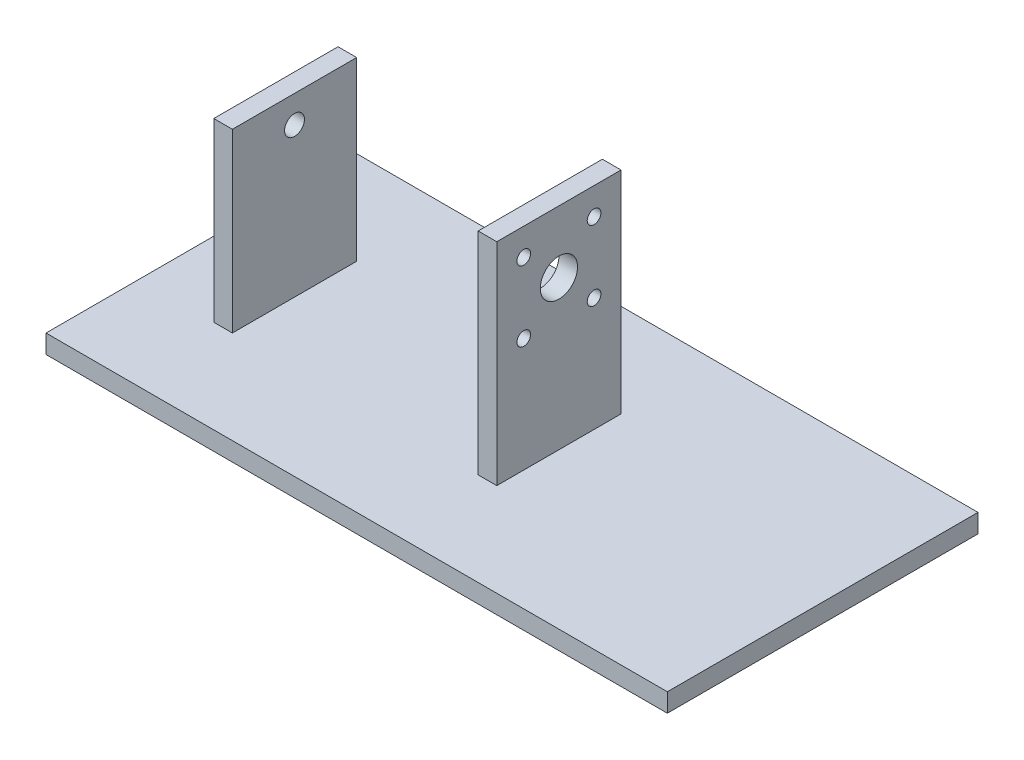
SolidWorks part; units mm, degrees
ref_plane "Front Plane" through (0, 0, 0) normal (0, 0, 1) x (1, 0, 0)
ref_plane "Top Plane" through (0, 0, 0) normal (0, 1, 0) x (1, 0, 0)
ref_plane "Right Plane" through (0, 0, 0) normal (1, 0, 0) x (0, 0, -1)
sketch "Sketch1" plane through (0, 0, 0) normal (0, 1, 0) x (1, 0, 0)
  line L1 (50, 25) -> (-50, 25)
  line L2 (50, 25) -> (50, -25)
  line L3 (50, -25) -> (-50, -25)
  line L4 (-50, 25) -> (-50, -25)
  line L5 (50, 25) -> (-50, -25) construction
  line L6 (50, -25) -> (-50, 25) construction
  line L7 (-38, 10) -> (-35, 10)
  line L8 (-38, 10) -> (-38, -10)
  line L9 (-38, -10) -> (-35, -10)
  line L10 (-35, 10) -> (-35, -10)
  line L11 (4.55, 10) -> (7.55, 10)
  line L12 (4.55, 10) -> (4.55, -10)
  line L13 (4.55, -10) -> (7.55, -10)
  line L14 (7.55, 10) -> (7.55, -10)
  point P0 (0, 0)
  point P14 (-35, 0)
  point P15 (7.55, 0)
  dimension "D1" = 100
  dimension "D2" = 50
  dimension "D3" = 39.55
  dimension "D4" = 3
  dimension "D5" = 20
  dimension "D6" = 12
extrude "Boss-Extrude1" add sketch "Sketch1" along normal blind 3 contours L7 L10 L9 L4 L3 L2 L1 L11 L14 L13 L12 region at (0.3744, 0, 0)
extrude "Boss-Extrude2" add sketch "Sketch1<3>" along normal blind 37 contours L14 L11 L12 L13 region at (6.05, 0, 0)
sketch "Sketch1<3>" plane through (0, 0, 0) normal (0, 1, 0) x (1, 0, 0) same geometry as "Sketch1"
extrude "Boss-Extrude3" add sketch "Sketch1<4>" along normal blind 31.4 contours L10 L9 L8 L7
sketch "Sketch1<4>" plane through (0, 0, 0) normal (0, 1, 0) x (1, 0, 0) same geometry as "Sketch1"
sketch "Sketch2" plane through (7.55, 0, 0) normal (1, 0, 0) x (0, 0, -1)
  line L0 (-10, 37) -> (10, 17) construction
  line L1 (10, 37) -> (10, 3) construction
  line L2 (10, 37) -> (-10, 17) construction
  line L3 (-10, 37) -> (-10, 3) construction
  line L4 (0, 27) -> (5.6569, 32.6569) construction
  line L5 (25, 3) -> (-25, 3) construction
  circle A0 centre (0, 27) radius 3
  circle A1 centre (5.6569, 32.6569) radius 1.1
  dimension "D2" = 6
  dimension "D4" = 2.2
  dimension "D1" = 20
  dimension "D3" = 8
  dimension "D5" = 45
extrude "Cut-Extrude1" cut sketch "Sketch2" against normal up to surface (3 mm away) up to face at (4.55, 20, 0)
pattern_circular "CirPattern1" count 4 over 360 about axis through (7.55, 27, 0) along (1, 0, 0) of "Cut-Extrude1"
sketch "Sketch3" plane through (-50, 0, 0) normal (-1, 0, 0) x (0, 0, 1)
  line L0 (10, 37) -> (-10, 17) construction
  circle A0 centre (0, 27) radius 1.6
  dimension "D1" = 3.2
extrude "Cut-Extrude2" cut sketch "Sketch3" against normal up to surface (15 mm away) up to face at (-35, 17.2, 0)
move or copy body "Body-Move/Copy1" [suppressed] bodies to move or copy 106
